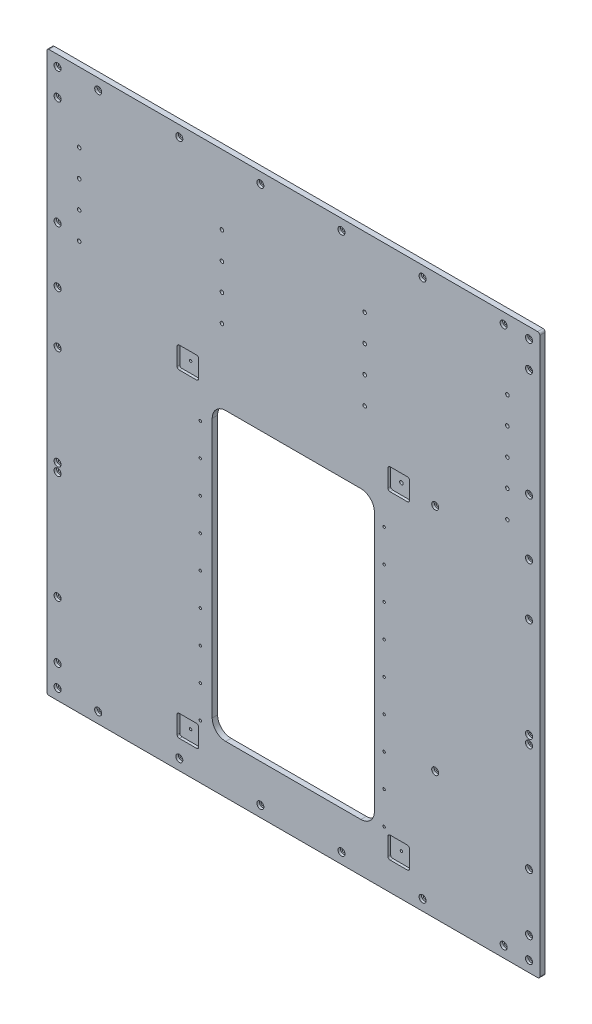
SolidWorks part; units mm, degrees
note: '?' marks a value the reader was unsure of.
ref_plane "Plan de face" through (0, 0, 0) normal (0, 0, 1) x (1, 0, 0)
ref_plane "Plan de dessus" through (0, 0, 0) normal (0, 1, 0) x (1, 0, 0)
ref_plane "Plan de droite" through (0, 0, 0) normal (1, 0, 0) x (0, 0, -1)
sketch "Esquisse1" plane through (0, 0, 0) normal (0, 0, 1) x (1, 0, 0)
  line L1 (-452, -517.5) -> (452, -517.5)
  line L2 (-456, -513.5) -> (-456, 513.5)
  line L3 (-452, 517.5) -> (452, 517.5)
  line L4 (456, -513.5) -> (456, 513.5)
  line L5 (-456, -517.5) -> (456, 517.5) construction
  line L6 (-456, 517.5) -> (456, -517.5) construction
  line L7 (0, 282.5) -> (0, -517.5) construction
  line L8 (-456, 0) -> (456, 0) construction
  arc A0 (-456, 513.5) -> (-452, 517.5) centre (-452, 513.5) cw
  arc A1 (456, 513.5) -> (452, 517.5) centre (452, 513.5) ccw
  arc A2 (452, -517.5) -> (456, -513.5) centre (452, -513.5) ccw
  arc A3 (-456, -513.5) -> (-452, -517.5) centre (-452, -513.5) ccw
  point P0 (0, 0)
  dimension "D3" = 4
  dimension "D4" = 4
  dimension "D5" = 4
  dimension "D6" = 4
  dimension "D1" = 912
  dimension "D2" = 1035
extrude "Boss.-Extru.1" add sketch "Esquisse1" along normal blind 10
sketch "Esquisse2" plane through (0, 0, 10) normal (0, 0, 1) x (1, 0, 0)
  line L0 (-125, -427.5) -> (125, -427.5)
  line L1 (-150, -402.5) -> (-150, 77.5)
  line L2 (150, -402.5) -> (150, 77.5)
  line L3 (-125, 102.5) -> (125, 102.5)
  line L4 (-125, -402.5) -> (125, 77.5) construction
  line L5 (-452, -517.5) -> (452, -517.5) construction
  arc A0 (-125, 102.5) -> (-150, 77.5) centre (-125, 77.5) ccw
  arc A1 (125, 102.5) -> (150, 77.5) centre (125, 77.5) cw
  arc A2 (150, -402.5) -> (125, -427.5) centre (125, -402.5) cw
  arc A3 (-150, -402.5) -> (-125, -427.5) centre (-125, -402.5) ccw
  point P9 (150, 102.5)
  point P12 (150, -427.5)
  dimension "D3" = 300
  dimension "D2" = 25
  dimension "D1" = 530
  dimension "D4" = 90
extrude "Enlèv. mat.-Extru.1" cut sketch "Esquisse2" against normal through all
hole_wizard "Dégagement M61" [suppressed] positions "Esquisse4" profile "Esquisse3" hole size "M6" standard "JIS"
sketch "Esquisse4" plane through (0, 0, 10) normal (0, 0, 1) x (1, 0, 0)
  point P0 (-277.4372, 232)
  point P2 (-247.5898, 232)
  point P4 (-247.5898, 201.8404)
  point P6 (-277.6003, 201.8404)
  point P8 (-262.5, 217)
sketch "Esquisse3" plane through (-277.4372, 232, 10) normal (1, 0, 0) x (0, -1, 0)
  line L0 (0, 0) -> (0, 10)
  line L1 (0, 10) -> (3.3, 10)
  line L2 (3.3, 10) -> (3.3, 0)
  line L5 (3.3, 0) -> (0, 0)
  line L11 (0, -6.35) -> (0, 107.95) construction
  dimension "Diamètre du perçage jusqu'au prochain" = 6.6
  dimension "Profondeur du perçage jusqu'au prochain" = 10
pattern_linear "Répétition linéaire1" [suppressed] count 2 spacing 245
hole_wizard "Chambrage pour vis à tête ronde bombée M61" [suppressed] positions "Esquisse6" profile "Esquisse5" counterbore size "M6" standard "Ansi Metric"
sketch "Esquisse6" plane through (0, 0, 0) normal (0, 0, -1) x (-1, 0, 0)
  point P0 (247.5898, 232)
  point P2 (277.4372, 232)
  point P4 (277.6003, 201.8404)
  point P6 (247.5898, 201.8404)
  point P8 (262.5, 217)
  point P10 (247.5898, -13)
  point P12 (277.4372, -13)
  point P14 (262.5, -28)
sketch "Esquisse5" plane through (-247.5898, 232, 0) normal (1, 0, 0) x (0, 1, 0)
  line L0 (0, 0) -> (0, 10)
  line L1 (0, 10) -> (3.3, 10)
  line L2 (3.3, 4.625) -> (3.3, 10)
  line L3 (3.3, 4.625) -> (3.325, 4.6)
  line L4 (3.325, 4.6) -> (6.5, 4.6)
  line L5 (6.5, 4.6) -> (6.5, 0)
  line L7 (0, 0) -> (6.5, 0)
  line L9 (-3.3, 4.625) -> (-3.325, 4.6) construction
  line L11 (0, -6.35) -> (0, 107.95) construction
  dimension "Diamètre du perçage jusqu'au prochain" = 6.6
  dimension "Profondeur du perçage jusqu'au prochain" = 10
  dimension "Diamètre du chambrage" = 13
  dimension "Profondeur du chambrage" = 4.6
  dimension "Diamètre du fraisage milieu" = 6.65
  dimension "Angle du fraisage milieu" = 90
hole_wizard "Chambrage pour vis à tête ronde bombée M62" [suppressed] positions "Esquisse8" profile "Esquisse7" counterbore size "M6" standard "Ansi Metric"
sketch "Esquisse8" plane through (0, 0, 0) normal (0, 0, -1) x (-1, 0, 0)
  point P0 (247.5898, -43.1596)
  point P2 (277.6003, -43.1596)
sketch "Esquisse7" plane through (-247.5898, -43.1596, 0) normal (1, 0, 0) x (0, 1, 0)
  line L0 (0, 0) -> (0, 10)
  line L1 (0, 10) -> (3.3, 10)
  line L2 (3.3, 4.625) -> (3.3, 10)
  line L3 (3.3, 4.625) -> (3.325, 4.6)
  line L4 (3.325, 4.6) -> (6.5, 4.6)
  line L5 (6.5, 4.6) -> (6.5, 0)
  line L7 (0, 0) -> (6.5, 0)
  line L9 (-3.3, 4.625) -> (-3.325, 4.6) construction
  line L11 (0, -6.35) -> (0, 107.95) construction
  dimension "Diamètre du perçage jusqu'au prochain" = 6.6
  dimension "Profondeur du perçage jusqu'au prochain" = 10
  dimension "Diamètre du chambrage" = 13
  dimension "Profondeur du chambrage" = 4.6
  dimension "Diamètre du fraisage milieu" = 6.65
  dimension "Angle du fraisage milieu" = 90
hole_wizard "Dégagement M62" [suppressed] positions "Esquisse10" profile "Esquisse9" hole size "M6" standard "JIS"
sketch "Esquisse10" plane through (0, 0, 0) normal (0, 0, -1) x (-1, 0, 0)
  point P0 (-209.6182, 209)
  point P2 (-180.0241, 209)
  point P4 (-180.0241, 179.1391)
  point P6 (-209.6182, 179)
  point P8 (-195, 194)
sketch "Esquisse9" plane through (209.6182, 209, 0) normal (1, 0, 0) x (0, 1, 0)
  line L0 (0, 0) -> (0, 10)
  line L1 (0, 10) -> (3.3, 10)
  line L2 (3.3, 10) -> (3.3, 0)
  line L5 (3.3, 0) -> (0, 0)
  line L11 (0, -6.35) -> (0, 107.95) construction
  dimension "Diamètre du perçage jusqu'au prochain" = 6.6
  dimension "Profondeur du perçage jusqu'au prochain" = 10
pattern_linear "Répétition linéaire2" [suppressed] count 2 spacing 390 count 2 spacing 380
hole_wizard "Chambrage pour vis à tête ronde bombée M63" [suppressed] positions "Esquisse14" profile "Esquisse13" counterbore size "M6" standard "Ansi Metric"
sketch "Esquisse14" plane through (0, 0, 10) normal (0, 0, 1) x (1, 0, 0)
  point P0 (-209.9759, 209)
  point P2 (-180.3818, 209)
  point P4 (-180.3818, 179)
  point P6 (-209.9759, 179)
  point P8 (-195, 194)
sketch "Esquisse13" plane through (-209.9759, 209, 10) normal (1, 0, 0) x (0, -1, 0)
  line L0 (0, 0) -> (0, 10)
  line L1 (0, 10) -> (3.3, 10)
  line L2 (3.3, 4.625) -> (3.3, 10)
  line L3 (3.3, 4.625) -> (3.325, 4.6)
  line L4 (3.325, 4.6) -> (6.5, 4.6)
  line L5 (6.5, 4.6) -> (6.5, 0)
  line L7 (0, 0) -> (6.5, 0)
  line L9 (-3.3, 4.625) -> (-3.325, 4.6) construction
  line L11 (0, -6.35) -> (0, 107.95) construction
  dimension "Diamètre du perçage jusqu'au prochain" = 6.6
  dimension "Profondeur du perçage jusqu'au prochain" = 10
  dimension "Diamètre du chambrage" = 13
  dimension "Profondeur du chambrage" = 4.6
  dimension "Diamètre du fraisage milieu" = 6.65
  dimension "Angle du fraisage milieu" = 90
pattern_linear "Répétition linéaire3" [suppressed] count 2 spacing 390 count 2 spacing 380
pattern_linear "Répétition linéaire4" [suppressed] count 2 spacing 27
hole_wizard "Dégagement M63" [suppressed] positions "Esquisse16" profile "Esquisse15" hole size "M6" standard "JIS"
sketch "Esquisse16" plane through (0, 0, 0) normal (0, 0, -1) x (-1, 0, 0)
  point P0 (-195, 109.5)
  point P2 (-209.9493, 94.5)
  point P4 (-209.9493, 124.6707)
  point P6 (-180.2902, 124.6707)
  point P8 (-180.2902, 94.5)
sketch "Esquisse15" plane through (195, 109.5, 0) normal (1, 0, 0) x (0, 1, 0)
  line L0 (0, 0) -> (0, 10)
  line L1 (0, 10) -> (3.3, 10)
  line L2 (3.3, 10) -> (3.3, 0)
  line L5 (3.3, 0) -> (0, 0)
  line L11 (0, -6.35) -> (0, 107.95) construction
  dimension "Diamètre du perçage jusqu'au prochain" = 6.6
  dimension "Profondeur du perçage jusqu'au prochain" = 10
pattern_linear "Répétition linéaire5" [suppressed] count 2 spacing 390 count 2 spacing 555
hole_wizard "Dégagement M41" positions "Esquisse24" profile "Esquisse23" hole size "M4" standard "JIS" end condition through all
sketch "Esquisse24" plane through (0, 0, 10) normal (0, 0, 1) x (1, 0, 0)
  point P0 (-172, -417.5)
sketch "Esquisse23" plane through (-172, -417.5, 10) normal (1, 0, 0) x (0, -1, 0)
  line L0 (0, 0) -> (0, 10)
  line L1 (0, 10) -> (2.25, 10)
  line L2 (2.25, 10) -> (2.25, 0)
  line L5 (2.25, 0) -> (0, 0)
  line L11 (0, -6.35) -> (0, 107.95) construction
  dimension "Diamètre du perçage jusqu'au prochain" = 4.5
  dimension "Profondeur du perçage jusqu'au prochain" = 10
pattern_linear "Répétition linéaire8" count 9 spacing 60 along (0, 1, 0) count 2 spacing 340 along (1, 0, 0) of "Dégagement M41"
hole_wizard "Dégagement M65" positions "Esquisse26" profile "Esquisse25" hole size "M6" standard "JIS" end condition through all
sketch "Esquisse26" plane through (0, 0, 0) normal (0, 0, -1) x (-1, 0, 0)
  point P0 (-436, 497.5)
  point P10 (-436, 448.2864)
  point P12 (-389.1232, 497.5)
  point P18 (-436, -457.5)
  point P20 (-436, -497.5)
  point P26 (-389.1232, -497.5)
  point P32 (436, -457.5)
  point P34 (436, -497.5)
sketch "Esquisse25" plane through (436, 497.5, 0) normal (1, 0, 0) x (0, 1, 0)
  line L0 (0, 0) -> (0, 10)
  line L1 (0, 10) -> (3.3, 10)
  line L2 (3.3, 10) -> (3.3, 0)
  line L5 (3.3, 0) -> (0, 0)
  line L11 (0, -6.35) -> (0, 107.95) construction
  dimension "Diamètre du perçage jusqu'au prochain" = 6.6
  dimension "Profondeur du perçage jusqu'au prochain" = 10
hole_wizard "Chambrage pour vis à tête ronde bombée M66" positions "Esquisse28" profile "Esquisse27" counterbore size "M6" standard "Ansi Metric" end condition through all
sketch "Esquisse28" plane through (0, 0, 10) normal (0, 0, 1) x (1, 0, 0)
  point P0 (436, 497.5)
sketch "Esquisse27" plane through (436, 497.5, 10) normal (1, 0, 0) x (0, -1, 0)
  line L0 (0, 0) -> (0, 10)
  line L1 (0, 10) -> (3.3, 10)
  line L2 (3.3, 4.625) -> (3.3, 10)
  line L3 (3.3, 4.625) -> (3.325, 4.6)
  line L4 (3.325, 4.6) -> (6.5, 4.6)
  line L5 (6.5, 4.6) -> (6.5, 0)
  line L7 (0, 0) -> (6.5, 0)
  line L9 (-3.3, 4.625) -> (-3.325, 4.6) construction
  line L11 (0, -6.35) -> (0, 107.95) construction
  dimension "Diamètre du perçage jusqu'au prochain" = 6.6
  dimension "Profondeur du perçage jusqu'au prochain" = 10
  dimension "Diamètre du chambrage" = 13
  dimension "Profondeur du chambrage" = 4.6
  dimension "Diamètre du fraisage milieu" = 6.65
  dimension "Angle du fraisage milieu" = 90
pattern_linear "Répétition linéaire9" count 2 spacing 872 along (-1, 0, 0) of "Chambrage pour vis à tête ronde bombée M66"
hole_wizard "Chambrage pour vis à tête ronde bombée M67" positions "Esquisse30" profile "Esquisse29" counterbore size "M6" standard "Ansi Metric" end condition through all
sketch "Esquisse30" plane through (0, 0, 10) normal (0, 0, 1) x (1, 0, 0)
  point P0 (389.1232, 497.5)
sketch "Esquisse29" plane through (389.1232, 497.5, 10) normal (1, 0, 0) x (0, -1, 0)
  line L0 (0, 0) -> (0, 10)
  line L1 (0, 10) -> (3.3, 10)
  line L2 (3.3, 4.625) -> (3.3, 10)
  line L3 (3.3, 4.625) -> (3.325, 4.6)
  line L4 (3.325, 4.6) -> (6.5, 4.6)
  line L5 (6.5, 4.6) -> (6.5, 0)
  line L7 (0, 0) -> (6.5, 0)
  line L9 (-3.3, 4.625) -> (-3.325, 4.6) construction
  line L11 (0, -6.35) -> (0, 107.95) construction
  dimension "Diamètre du perçage jusqu'au prochain" = 6.6
  dimension "Profondeur du perçage jusqu'au prochain" = 10
  dimension "Diamètre du chambrage" = 13
  dimension "Profondeur du chambrage" = 4.6
  dimension "Diamètre du fraisage milieu" = 6.65
  dimension "Angle du fraisage milieu" = 90
pattern_linear "Répétition linéaire10" count 6 spacing 150 along (-1, 0, 0) of "Chambrage pour vis à tête ronde bombée M67"
hole_wizard "Chambrage pour vis à tête ronde bombée M68" positions "Esquisse32" profile "Esquisse31" counterbore size "M6" standard "Ansi Metric" end condition through all
sketch "Esquisse32" plane through (0, 0, 10) normal (0, 0, 1) x (1, 0, 0)
  point P0 (436, 448.2864)
sketch "Esquisse31" plane through (436, 448.2864, 10) normal (1, 0, 0) x (0, -1, 0)
  line L0 (0, 0) -> (0, 10)
  line L1 (0, 10) -> (3.3, 10)
  line L2 (3.3, 4.625) -> (3.3, 10)
  line L3 (3.3, 4.625) -> (3.325, 4.6)
  line L4 (3.325, 4.6) -> (6.5, 4.6)
  line L5 (6.5, 4.6) -> (6.5, 0)
  line L7 (0, 0) -> (6.5, 0)
  line L9 (-3.3, 4.625) -> (-3.325, 4.6) construction
  line L11 (0, -6.35) -> (0, 107.95) construction
  dimension "Diamètre du perçage jusqu'au prochain" = 6.6
  dimension "Profondeur du perçage jusqu'au prochain" = 10
  dimension "Diamètre du chambrage" = 13
  dimension "Profondeur du chambrage" = 4.6
  dimension "Diamètre du fraisage milieu" = 6.65
  dimension "Angle du fraisage milieu" = 90
pattern_linear "Répétition linéaire11" count 5 spacing 200 along (0, -1, 0) count 2 spacing 872 along (-1, 0, 0) of "Chambrage pour vis à tête ronde bombée M68"
hole_wizard "Chambrage pour vis à tête ronde bombée M69" positions "Esquisse34" profile "Esquisse33" counterbore size "M6" standard "Ansi Metric" end condition through all
sketch "Esquisse34" plane through (0, 0, 10) normal (0, 0, 1) x (1, 0, 0)
  point P0 (436, -457.5)
  point P2 (436, -497.5)
sketch "Esquisse33" plane through (436, -457.5, 10) normal (1, 0, 0) x (0, -1, 0)
  line L0 (0, 0) -> (0, 10)
  line L1 (0, 10) -> (3.3, 10)
  line L2 (3.3, 4.625) -> (3.3, 10)
  line L3 (3.3, 4.625) -> (3.325, 4.6)
  line L4 (3.325, 4.6) -> (6.5, 4.6)
  line L5 (6.5, 4.6) -> (6.5, 0)
  line L7 (0, 0) -> (6.5, 0)
  line L9 (-3.3, 4.625) -> (-3.325, 4.6) construction
  line L11 (0, -6.35) -> (0, 107.95) construction
  dimension "Diamètre du perçage jusqu'au prochain" = 6.6
  dimension "Profondeur du perçage jusqu'au prochain" = 10
  dimension "Diamètre du chambrage" = 13
  dimension "Profondeur du chambrage" = 4.6
  dimension "Diamètre du fraisage milieu" = 6.65
  dimension "Angle du fraisage milieu" = 90
pattern_linear "Répétition linéaire13" count 2 spacing 872 along (-1, 0, 0) of "Chambrage pour vis à tête ronde bombée M69"
hole_wizard "Chambrage pour vis à tête ronde bombée M610" positions "Esquisse36" profile "Esquisse35" counterbore size "M6" standard "Ansi Metric" end condition through all
sketch "Esquisse36" plane through (0, 0, 10) normal (0, 0, 1) x (1, 0, 0)
  point P0 (389.1232, -497.5)
sketch "Esquisse35" plane through (389.1232, -497.5, 10) normal (1, 0, 0) x (0, -1, 0)
  line L0 (0, 0) -> (0, 10)
  line L1 (0, 10) -> (3.3, 10)
  line L2 (3.3, 4.625) -> (3.3, 10)
  line L3 (3.3, 4.625) -> (3.325, 4.6)
  line L4 (3.325, 4.6) -> (6.5, 4.6)
  line L5 (6.5, 4.6) -> (6.5, 0)
  line L7 (0, 0) -> (6.5, 0)
  line L9 (-3.3, 4.625) -> (-3.325, 4.6) construction
  line L11 (0, -6.35) -> (0, 107.95) construction
  dimension "Diamètre du perçage jusqu'au prochain" = 6.6
  dimension "Profondeur du perçage jusqu'au prochain" = 10
  dimension "Diamètre du chambrage" = 13
  dimension "Profondeur du chambrage" = 4.6
  dimension "Diamètre du fraisage milieu" = 6.65
  dimension "Angle du fraisage milieu" = 90
pattern_linear "Répétition linéaire14" count 6 spacing 150 along (-1, 0, 0) of "Chambrage pour vis à tête ronde bombée M610"
sketch "Esquisse41" plane through (0, 0, 10) normal (0, 0, 1) x (1, 0, 0)
  line L0 (452, 517.5) -> (-452, 517.5) construction
  line L1 (-456, 513.5) -> (-456, -513.5) construction
  circle A0 centre (-436, 144.5) radius 1.5
  circle A1 centre (-436, -136.5) radius 1.5
  dimension "D1" = 3
  dimension "D2" = 373
  dimension "D3" = 20
  dimension "D4" = 2
extrude "Enlèv. mat.-Extru.2" cut sketch "Esquisse41" against normal through all
ref_point "Point1"
ref_axis "Axe1" through (0, 517.5, 5) along (0, 1, 0)?
ref_plane "Plan1" through (0, 0, 0) normal (1, 0, 0) x (0, 1, 0)
mirror "Symétrie1" about plane through (0, 0, 0) normal (1, 0, 0) of "Enlèv. mat.-Extru.2"
hole_wizard "Chambrage pour vis à tête ronde bombée M611" positions "Esquisse43" profile "Esquisse44" counterbore size "M6" standard "Ansi Metric" end condition through all
sketch "Esquisse43" plane through (0, 0, 10) normal (0, 0, 1) x (1, 0, 0)
  point P0 (-436, 144.5)
  point P4 (-436, -136.5)
  point P7 (436, -136.5)
  point P10 (436, 144.5)
sketch "Esquisse44" plane through (-436, 144.5, 10) normal (1, 0, 0) x (0, -1, 0)
  line L0 (0, 0) -> (0, 10)
  line L1 (0, 10) -> (3.3, 10)
  line L2 (3.3, 4.625) -> (3.3, 10)
  line L3 (3.3, 4.625) -> (3.325, 4.6)
  line L4 (3.325, 4.6) -> (6.5, 4.6)
  line L5 (6.5, 4.6) -> (6.5, 0)
  line L7 (0, 0) -> (6.5, 0)
  line L9 (-3.3, 4.625) -> (-3.325, 4.6) construction
  line L11 (0, -6.35) -> (0, 107.95) construction
  dimension "Diamètre du perçage jusqu'au prochain" = 6.6
  dimension "Profondeur du perçage jusqu'au prochain" = 10
  dimension "Diamètre du chambrage" = 13
  dimension "Profondeur du chambrage" = 4.6
  dimension "Diamètre du fraisage milieu" = 6.65
  dimension "Angle du fraisage milieu" = 90
hole_wizard "Dégagement M67" positions "Esquisse46" profile "Esquisse45" hole size "M6" standard "JIS" end condition through all
sketch "Esquisse46" plane through (0, 0, 0) normal (0, 0, -1) x (-1, 0, 0)
  point P0 (-396.0014, 188.3978)
sketch "Esquisse45" plane through (396.0014, 188.3978, 0) normal (1, 0, 0) x (0, 1, 0)
  line L0 (0, 0) -> (0, 10)
  line L1 (0, 10) -> (3.3, 10)
  line L2 (3.3, 10) -> (3.3, 0)
  line L5 (3.3, 0) -> (0, 0)
  line L11 (0, -6.35) -> (0, 107.95) construction
  dimension "Diamètre du perçage jusqu'au prochain" = 6.6
  dimension "Profondeur du perçage jusqu'au prochain" = 10
pattern_linear "Répétition linéaire15" count 4 spacing 264 along (-1, 0, 0) count 5 spacing 50 along (0, 1, 0) skipping (1, 0), (2, 0), (3, 0) of "Dégagement M67"
hole_wizard "Dégagement M68" positions "Esquisse48" profile "Esquisse47" hole size "M6" standard "JIS" end condition through all
sketch "Esquisse48" plane through (0, 0, 0) normal (0, 0, -1) x (-1, 0, 0)
  point P9 (-195, 144.5)
sketch "Esquisse47" plane through (195, 144.5, 0) normal (1, 0, 0) x (0, 1, 0)
  line L0 (0, 0) -> (0, 10)
  line L1 (0, 10) -> (3.3, 10)
  line L2 (3.3, 10) -> (3.3, 0)
  line L5 (3.3, 0) -> (0, 0)
  line L11 (0, -6.35) -> (0, 107.95) construction
  dimension "Diamètre du perçage jusqu'au prochain" = 6.6
  dimension "Profondeur du perçage jusqu'au prochain" = 10
hole_wizard "Chambrage pour vis à tête ronde bombée M41" positions "Esquisse50" profile "Esquisse49" counterbore size "M4" standard "Ansi Metric" end condition through all
sketch "Esquisse50" plane through (0, 0, 10) normal (0, 0, 1) x (1, 0, 0)
  point P4 (195, 144.5)
sketch "Esquisse49" plane through (195, 144.5, 10) normal (1, 0, 0) x (0, -1, 0)
  line L0 (0, 0) -> (0, 10)
  line L1 (0, 10) -> (2.25, 10)
  line L2 (2.25, 3.125) -> (2.25, 10)
  line L3 (2.25, 3.125) -> (2.275, 3.1)
  line L4 (2.275, 3.1) -> (4.5, 3.1)
  line L5 (4.5, 3.1) -> (4.5, 0)
  line L7 (0, 0) -> (4.5, 0)
  line L9 (-2.25, 3.125) -> (-2.275, 3.1) construction
  line L11 (0, -6.35) -> (0, 107.95) construction
  dimension "Diamètre du perçage jusqu'au prochain" = 4.5
  dimension "Profondeur du perçage jusqu'au prochain" = 10
  dimension "Diamètre du chambrage" = 9
  dimension "Profondeur du chambrage" = 3.1
  dimension "Diamètre du fraisage milieu" = 4.55
  dimension "Angle du fraisage milieu" = 90
pattern_linear "Répétition linéaire16" count 2 spacing 390 along (-1, 0, 0) count 2 spacing 590 along (0, -1, 0) of "Chambrage pour vis à tête ronde bombée M41"
sketch "Esquisse51" plane through (0, 0, 0) normal (0, 0, 1) x (1, 0, 0)
  spline S0 degree 1 poles (246.5761, 163.5395) (278.5761, 163.5395) knots 0 0 1 1
  spline S1 degree 2 poles (278.5761, 163.5395) (282.2329, 163.1964) (282.5761, 159.5395) knots 0 0 0 1 1 1
  spline S2 degree 2 poles (282.5761, 159.5395) (282.5761, 144.5111) (282.5761, 127.5395) knots 0 0 0 1 1 1
  spline S3 degree 2 poles (282.5761, 127.5395) (282.2329, 123.8826) (278.5761, 123.5395) knots 0 0 0 1 1 1
  spline S4 degree 1 poles (278.5761, 123.5395) (246.5761, 123.5395) knots 0 0 1 1
  spline S5 degree 2 poles (246.5761, 123.5395) (242.9192, 123.8826) (242.5761, 127.5395) knots 0 0 0 1 1 1
  spline S6 degree 1 poles (242.5761, 127.5395) (242.5761, 159.5395) knots 0 0 1 1
  spline S7 degree 2 poles (242.5761, 159.5395) (242.9192, 163.1964) (246.5761, 163.5395) knots 0 0 0 1 1 1
sketch "Esquisse52" plane through (0, 0, 10) normal (0, 0, -1) x (-1, 0, 0)
  spline S0 degree 1 poles (-211, -425.5) (-179, -425.5) knots 0 0 1 1
  spline S1 degree 2 poles (-179, -425.5) (-175.3431, -425.8431) (-175, -429.5) knots 0 0 0 1 1 1
  spline S2 degree 1 poles (-175, -429.5) (-175, -461.5) knots 0 0 1 1
  spline S3 degree 2 poles (-175, -461.5) (-175.3431, -465.1569) (-179, -465.5) knots 0 0 0 1 1 1
  spline S4 degree 1 poles (-179, -465.5) (-211, -465.5) knots 0 0 1 1
  spline S5 degree 2 poles (-211, -465.5) (-214.6569, -465.1569) (-215, -461.5) knots 0 0 0 1 1 1
  spline S6 degree 1 poles (-215, -461.5) (-215, -429.5) knots 0 0 1 1
  spline S7 degree 2 poles (-215, -429.5) (-214.6569, -425.8431) (-211, -425.5) knots 0 0 0 1 1 1
extrude "Enlèv. mat.-Extru.6" cut sketch "Esquisse52" along normal blind 5
pattern_linear "Répétition linéaire18" count 2 spacing 590 along (0, 1, 0) count 2 spacing 390 along (-1, 0, 0) of "Enlèv. mat.-Extru.6"
extrude "Enlèv. mat.-Extru.9" cut sketch "Esquisse51" along normal blind 5
pattern_linear "Répétition linéaire20" count 2 spacing 425 along (0, 1, 0) of "Enlèv. mat.-Extru.9"
hole_wizard "Dégagement M610" positions "Esquisse55" profile "Esquisse56" hole size "M6" standard "JIS" end condition through all
sketch "Esquisse55" plane through (0, 0, 0) normal (0, 0, -1) x (-1, 0, 0)
  point P0 (-262.5, 143.5)
sketch "Esquisse56" plane through (262.5, 143.5, 0) normal (1, 0, 0) x (0, 1, 0)
  line L0 (0, 0) -> (0, 10)
  line L1 (0, 10) -> (3.3, 10)
  line L2 (3.3, 10) -> (3.3, 0)
  line L5 (3.3, 0) -> (0, 0)
  line L11 (0, -6.35) -> (0, 107.95) construction
  dimension "Diamètre du perçage jusqu'au prochain" = 6.6
  dimension "Profondeur du perçage jusqu'au prochain" = 10
hole_wizard "Chambrage pour vis à tête ronde bombée M612" positions "Esquisse58" profile "Esquisse57" counterbore size "M6" standard "Ansi Metric" end condition through all
sketch "Esquisse58" plane through (0, 0, 10) normal (0, 0, 1) x (1, 0, 0)
  point P0 (262.5, 143.5)
sketch "Esquisse57" plane through (262.5, 143.5, 10) normal (1, 0, 0) x (0, -1, 0)
  line L0 (0, 0) -> (0, 10)
  line L1 (0, 10) -> (3.3, 10)
  line L2 (3.3, 4.625) -> (3.3, 10)
  line L3 (3.3, 4.625) -> (3.325, 4.6)
  line L4 (3.325, 4.6) -> (6.5, 4.6)
  line L5 (6.5, 4.6) -> (6.5, 0)
  line L7 (0, 0) -> (6.5, 0)
  line L9 (-3.3, 4.625) -> (-3.325, 4.6) construction
  line L11 (0, -6.35) -> (0, 107.95) construction
  dimension "Diamètre du perçage jusqu'au prochain" = 6.6
  dimension "Profondeur du perçage jusqu'au prochain" = 10
  dimension "Diamètre du chambrage" = 13
  dimension "Profondeur du chambrage" = 4.6
  dimension "Diamètre du fraisage milieu" = 6.65
  dimension "Angle du fraisage milieu" = 90
pattern_linear "Répétition linéaire21" count 2 spacing 425 along (0, -1, 0) of "Chambrage pour vis à tête ronde bombée M612"
